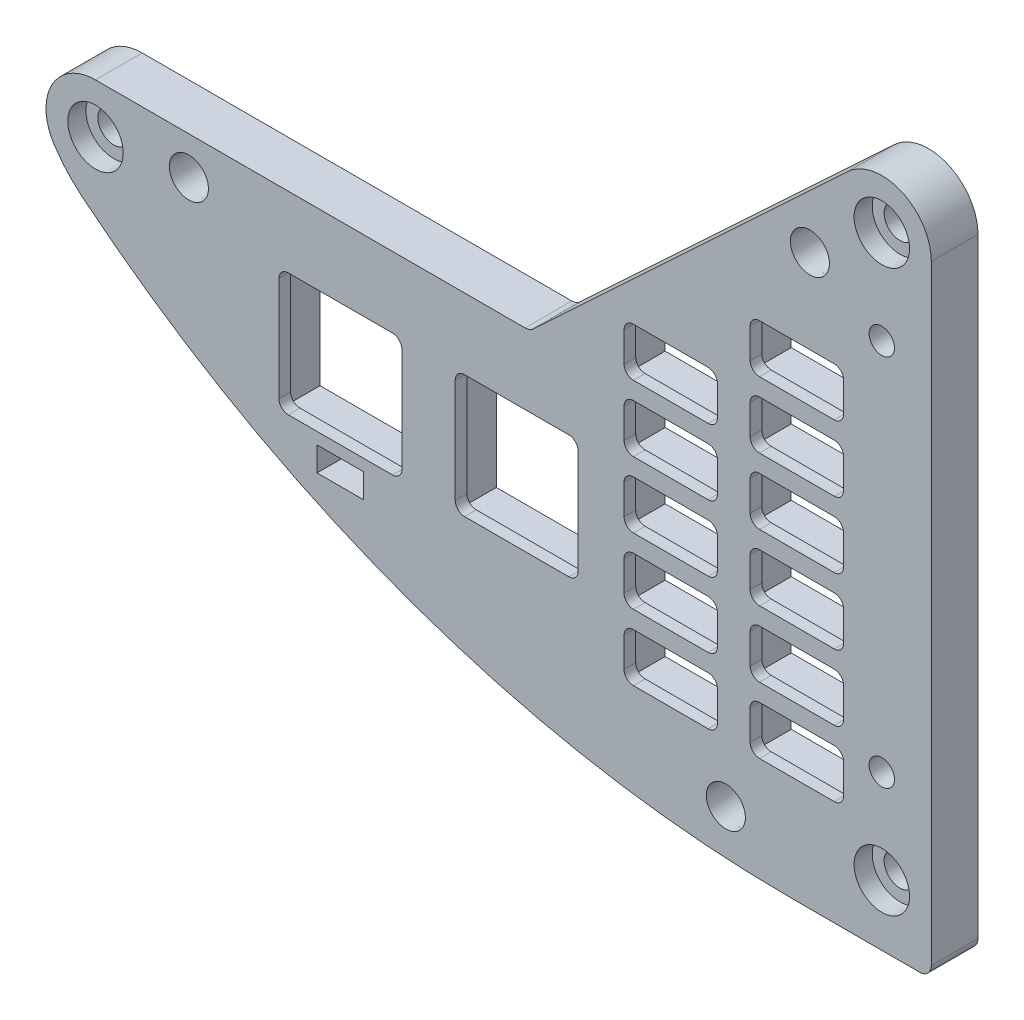
SolidWorks part; units mm, degrees
ref_plane "Front Plane" through (0, 0, 0) normal (0, 0, 1) x (1, 0, 0)
ref_plane "Top Plane" through (0, 0, 0) normal (0, 1, 0) x (1, 0, 0)
ref_plane "Right Plane" through (0, 0, 0) normal (1, 0, 0) x (0, 0, -1)
sketch "Sketch2" plane through (0, 0, -77.851) normal (0, 0, 1) x (1, 0, 0)
  line L0 (-595.8647, 521.6144) -> (-595.8647, 503.8344) construction
  line L1 (-595.8647, 503.8344) -> (-578.0847, 503.8344) construction
  line L2 (-578.0847, 503.8344) -> (-578.0847, 521.6144) construction
  line L3 (-578.0847, 521.6144) -> (-595.8647, 521.6144) construction
  line L4 (-530.5867, 481.6475) -> (-530.5867, 566.1727)
  line L5 (-541.9099, 571.0939) -> (-585.1967, 530.7013)
  line L6 (-585.1967, 530.7013) -> (-644.2517, 530.7013)
  line L7 (-549.6367, 481.6475) -> (-530.5867, 481.6475)
  line L8 (-530.5867, 481.6475) -> (-530.5867, 566.1727)
  line L9 (-541.9099, 571.0939) -> (-585.1967, 530.7013)
  line L10 (-585.1967, 530.7013) -> (-644.2517, 530.7013)
  line L11 (-549.6367, 481.6475) -> (-530.5867, 481.6475)
  line L12 (-572.3697, 495.935) -> (-559.6697, 495.935) construction
  line L13 (-559.6697, 495.935) -> (-559.6697, 502.539) construction
  line L14 (-559.6697, 502.539) -> (-572.3697, 502.539) construction
  line L15 (-572.3697, 502.539) -> (-572.3697, 495.935) construction
  line L16 (-572.3697, 504.9266) -> (-559.6697, 504.9266) construction
  line L17 (-559.6697, 504.9266) -> (-559.6697, 511.5306) construction
  line L18 (-559.6697, 511.5306) -> (-572.3697, 511.5306) construction
  line L19 (-572.3697, 511.5306) -> (-572.3697, 504.9266) construction
  line L20 (-555.2247, 502.539) -> (-555.2247, 495.935) construction
  line L21 (-555.2247, 495.935) -> (-542.5247, 495.935) construction
  line L22 (-542.5247, 495.935) -> (-542.5247, 502.539) construction
  line L23 (-542.5247, 502.539) -> (-555.2247, 502.539) construction
  line L24 (-555.2247, 504.9266) -> (-542.5247, 504.9266) construction
  line L25 (-542.5247, 504.9266) -> (-542.5247, 511.5306) construction
  line L26 (-542.5247, 511.5306) -> (-555.2247, 511.5306) construction
  line L27 (-555.2247, 511.5306) -> (-555.2247, 504.9266) construction
  line L28 (-555.2247, 513.9182) -> (-542.5247, 513.9182) construction
  line L29 (-542.5247, 513.9182) -> (-542.5247, 520.5222) construction
  line L30 (-542.5247, 520.5222) -> (-555.2247, 520.5222) construction
  line L31 (-555.2247, 520.5222) -> (-555.2247, 513.9182) construction
  line L32 (-572.3697, 513.9182) -> (-559.6697, 513.9182) construction
  line L33 (-559.6697, 513.9182) -> (-559.6697, 520.5222) construction
  line L34 (-559.6697, 520.5222) -> (-572.3697, 520.5222) construction
  line L35 (-572.3697, 520.5222) -> (-572.3697, 513.9182) construction
  line L36 (-572.3697, 522.9098) -> (-559.6697, 522.9098) construction
  line L37 (-559.6697, 522.9098) -> (-559.6697, 529.5138) construction
  line L38 (-559.6697, 529.5138) -> (-572.3697, 529.5138) construction
  line L39 (-572.3697, 529.5138) -> (-572.3697, 522.9098) construction
  line L40 (-555.2247, 522.9098) -> (-542.5247, 522.9098) construction
  line L41 (-542.5247, 522.9098) -> (-542.5247, 529.5138) construction
  line L42 (-542.5247, 529.5138) -> (-555.2247, 529.5138) construction
  line L43 (-555.2247, 529.5138) -> (-555.2247, 522.9098) construction
  line L44 (-555.2247, 531.9014) -> (-542.5247, 531.9014) construction
  line L45 (-542.5247, 531.9014) -> (-542.5247, 538.5054) construction
  line L46 (-542.5247, 538.5054) -> (-555.2247, 538.5054) construction
  line L47 (-555.2247, 538.5054) -> (-555.2247, 531.9014) construction
  line L48 (-572.3697, 531.9014) -> (-559.6697, 531.9014) construction
  line L49 (-559.6697, 531.9014) -> (-559.6697, 538.5054) construction
  line L50 (-559.6697, 538.5054) -> (-572.3697, 538.5054) construction
  line L51 (-572.3697, 538.5054) -> (-572.3697, 531.9014) construction
  line L52 (-555.2247, 540.893) -> (-542.5247, 540.893) construction
  line L53 (-542.5247, 540.893) -> (-542.5247, 547.497) construction
  line L54 (-542.5247, 547.497) -> (-555.2247, 547.497) construction
  line L55 (-555.2247, 547.497) -> (-555.2247, 540.893) construction
  line L56 (-555.2247, 513.9182) -> (-542.5247, 513.9182) construction
  line L57 (-595.8647, 521.6144) -> (-595.8647, 503.8344) construction
  line L58 (-595.8647, 503.8344) -> (-578.0847, 503.8344) construction
  line L59 (-578.0847, 503.8344) -> (-578.0847, 521.6144) construction
  line L60 (-578.0847, 521.6144) -> (-595.8647, 521.6144) construction
  line L61 (-572.3697, 495.935) -> (-559.6697, 495.935)
  line L62 (-559.6697, 495.935) -> (-559.6697, 502.539)
  line L63 (-559.6697, 502.539) -> (-572.3697, 502.539)
  line L64 (-572.3697, 502.539) -> (-572.3697, 495.935)
  line L65 (-572.3697, 504.9266) -> (-559.6697, 504.9266)
  line L66 (-559.6697, 504.9266) -> (-559.6697, 511.5306)
  line L67 (-559.6697, 511.5306) -> (-572.3697, 511.5306)
  line L68 (-572.3697, 511.5306) -> (-572.3697, 504.9266)
  line L69 (-555.2247, 502.539) -> (-555.2247, 495.935)
  line L70 (-555.2247, 495.935) -> (-542.5247, 495.935)
  line L71 (-542.5247, 495.935) -> (-542.5247, 502.539)
  line L72 (-542.5247, 502.539) -> (-555.2247, 502.539)
  line L73 (-555.2247, 504.9266) -> (-542.5247, 504.9266)
  line L74 (-542.5247, 504.9266) -> (-542.5247, 511.5306)
  line L75 (-542.5247, 511.5306) -> (-555.2247, 511.5306)
  line L76 (-555.2247, 511.5306) -> (-555.2247, 504.9266)
  line L77 (-555.2247, 513.9182) -> (-542.5247, 513.9182)
  line L78 (-542.5247, 513.9182) -> (-542.5247, 520.5222)
  line L79 (-542.5247, 520.5222) -> (-555.2247, 520.5222)
  line L80 (-555.2247, 520.5222) -> (-555.2247, 513.9182)
  line L81 (-572.3697, 513.9182) -> (-559.6697, 513.9182)
  line L82 (-559.6697, 513.9182) -> (-559.6697, 520.5222)
  line L83 (-559.6697, 520.5222) -> (-572.3697, 520.5222)
  line L84 (-572.3697, 520.5222) -> (-572.3697, 513.9182)
  line L85 (-572.3697, 522.9098) -> (-559.6697, 522.9098)
  line L86 (-559.6697, 522.9098) -> (-559.6697, 529.5138)
  line L87 (-559.6697, 529.5138) -> (-572.3697, 529.5138)
  line L88 (-572.3697, 529.5138) -> (-572.3697, 522.9098)
  line L89 (-555.2247, 522.9098) -> (-542.5247, 522.9098)
  line L90 (-542.5247, 522.9098) -> (-542.5247, 529.5138)
  line L91 (-542.5247, 529.5138) -> (-555.2247, 529.5138)
  line L92 (-555.2247, 529.5138) -> (-555.2247, 522.9098)
  line L93 (-555.2247, 531.9014) -> (-542.5247, 531.9014)
  line L94 (-542.5247, 531.9014) -> (-542.5247, 538.5054)
  line L95 (-542.5247, 538.5054) -> (-555.2247, 538.5054)
  line L96 (-555.2247, 538.5054) -> (-555.2247, 531.9014)
  line L97 (-572.3697, 531.9014) -> (-559.6697, 531.9014)
  line L98 (-559.6697, 531.9014) -> (-559.6697, 538.5054)
  line L99 (-559.6697, 538.5054) -> (-572.3697, 538.5054)
  line L100 (-572.3697, 538.5054) -> (-572.3697, 531.9014)
  line L101 (-555.2247, 540.893) -> (-542.5247, 540.893)
  line L102 (-542.5247, 540.893) -> (-542.5247, 547.497)
  line L103 (-542.5247, 547.497) -> (-555.2247, 547.497)
  line L104 (-555.2247, 547.497) -> (-555.2247, 540.893)
  line L105 (-555.2247, 513.9182) -> (-542.5247, 513.9182)
  line L106 (-578.0847, 503.8344) -> (-595.8647, 521.6144) construction
  line L108 (-578.6181, 521.081) -> (-595.3313, 521.081)
  line L109 (-578.6181, 521.081) -> (-578.6181, 504.3678)
  line L110 (-578.6181, 504.3678) -> (-595.3313, 504.3678)
  line L111 (-595.3313, 521.081) -> (-595.3313, 504.3678)
  line L112 (-578.6181, 521.081) -> (-595.3313, 504.3678) construction
  line L113 (-578.6181, 504.3678) -> (-595.3313, 521.081) construction
  arc A4 (-530.5867, 566.1727) -> (-541.9099, 571.0939) centre (-537.3177, 566.1727) ccw
  arc A5 (-644.2517, 530.7013) -> (-649.8762, 520.2727) centre (-644.2517, 523.9703) ccw
  arc A6 (-649.8762, 520.2727) -> (-646.0191, 515.9958) centre (-634.0129, 530.7013) ccw
  arc A7 (-646.0191, 515.9958) -> (-549.6367, 481.6475) centre (-549.6367, 634.0475) ccw
  arc A8 (-530.5867, 566.1727) -> (-541.9099, 571.0939) centre (-537.3177, 566.1727) ccw
  arc A9 (-644.2517, 530.7013) -> (-649.8762, 520.2727) centre (-644.2517, 523.9703) ccw
  arc A10 (-649.8762, 520.2727) -> (-646.0191, 515.9958) centre (-634.0129, 530.7013) ccw
  arc A11 (-646.0191, 515.9958) -> (-549.6367, 481.6475) centre (-549.6367, 634.0475) ccw
  point P58 (-586.9747, 512.7244)
  dimension "D2" = 16.7132
  dimension "D1" = 0
extrude "Boss-Extrude1" add sketch "Sketch2" against normal blind 6.35 contours A10 A11 L11 L8 A8 L9 L10 A9 L60 L59 L58 L57 L64 L63 L62 L61 L68 L67 L66 L65 L72 L71 L70 L69 L76 L75 L74 L73 L80 L79 L78 L77 L84 L83 L82 L81 L88 L87 L86 L85 L92 L91 region at (-576.7506, 517.828, -77.851)
hole_wizard "CBORE for #6 Pan Head Machine Screw1" positions "Sketch4" profile "Sketch3" counterbore size "#6" standard "ANSI Inch" end condition through all
sketch "Sketch4" plane through (0, 0, -77.851) normal (0, 0, 1) x (1, 0, 0)
  point P0 (-537.3177, 489.9025)
  point P3 (-537.3177, 566.1727)
  point P6 (-644.2517, 523.9703)
sketch "Sketch3" plane through (-537.3177, 489.9025, -77.851) normal (1, 0, 0) x (0, -1, 0)
  line L0 (0, 0) -> (0, 6.35)
  line L1 (0, 6.35) -> (2.1526, 6.35)
  line L3 (2.1526, 6.35) -> (2.1526, 2.4638)
  line L4 (2.1526, 2.4638) -> (3.7706, 2.4638)
  line L5 (3.7706, 2.4638) -> (3.7706, 0)
  line L7 (3.7706, 0) -> (0, 0)
  line L11 (0, -6.35) -> (0, 107.95) construction
  dimension "Thru Hole Dia." = 4.3053
  dimension "Thru Hole Depth" = 6.35
  dimension "C'Bore Dia." = 7.5413
  dimension "C'Bore Depth" = 2.4638
hole_wizard "#6 Threaded Insert Tapered Hole" positions "Sketch6" profile "Sketch5" legacy
sketch "Sketch6" plane through (0, 0, -77.851) normal (0, 0, 1) x (1, 0, 0)
  point P0 (-558.5267, 487.9975)
  point P3 (-547.0967, 558.9583)
  point P6 (-631.5517, 525.5578)
sketch "Sketch5" plane through (-558.5267, 487.9975, -77.851) normal (1, 0, 0) x (0, -1, 0)
  line L0 (0, 0) -> (0, 3.81)
  line L1 (0, 3.81) -> (2.5273, 3.81)
  line L2 (2.5273, 3.81) -> (2.6543, 0)
  line L3 (2.6543, 0) -> (0, 0)
  line L4 (0, 110) -> (0, -10) construction
  dimension "Minor Diameter" = 5.0546
  dimension "Depth" = 3.81
  dimension "Major Diameter" = 5.3086
sketch "Sketch7" plane through (0, 0, -77.851) normal (0, 0, 1) x (1, 0, 0)
  line L0 (-610.9485, 512.7244) -> (-610.9485, 521.081) construction
  line L2 (-610.9485, 512.7244) -> (-595.3313, 512.7244) construction
  line L3 (-602.5919, 504.3678) -> (-619.3051, 504.3678)
  line L4 (-602.5919, 504.3678) -> (-602.5919, 521.081)
  line L5 (-602.5919, 521.081) -> (-619.3051, 521.081)
  line L6 (-619.3051, 504.3678) -> (-619.3051, 521.081)
  line L7 (-602.5919, 504.3678) -> (-619.3051, 521.081) construction
  line L8 (-602.5919, 521.081) -> (-619.3051, 504.3678) construction
  line L9 (-595.3313, 521.081) -> (-595.3313, 504.3678) construction
  point P5 (-610.9485, 512.7244)
  dimension "D1" = 16.7132
  dimension "D2" = 16.7132
  dimension "D3" = 15.6171
extrude "Cut-Extrude1" cut sketch "Sketch7" against normal through all
sketch "Sketch8" plane through (0, 0, -84.201) normal (0, 0, -1) x (-1, 0, 0)
  line L0 (555.9867, 540.131) -> (555.9867, 548.259)
  line L1 (555.9867, 548.259) -> (541.7627, 548.259)
  line L2 (541.7627, 548.259) -> (541.7627, 540.131)
  line L3 (541.7627, 540.131) -> (555.9867, 540.131)
  line L4 (555.2247, 540.893) -> (555.2247, 547.497)
  line L5 (542.5247, 540.893) -> (555.2247, 540.893)
  line L6 (542.5247, 547.497) -> (542.5247, 540.893)
  line L7 (555.2247, 547.497) -> (542.5247, 547.497)
  line L8 (555.2247, 540.893) -> (555.2247, 547.497) construction
  line L9 (542.5247, 540.893) -> (555.2247, 540.893) construction
  line L10 (542.5247, 547.497) -> (542.5247, 540.893) construction
  line L11 (555.2247, 547.497) -> (542.5247, 547.497) construction
  line L12 (555.2247, 531.9014) -> (555.2247, 538.5054)
  line L13 (542.5247, 531.9014) -> (555.2247, 531.9014)
  line L14 (542.5247, 538.5054) -> (542.5247, 531.9014)
  line L15 (555.2247, 538.5054) -> (542.5247, 538.5054)
  line L16 (555.2247, 531.9014) -> (555.2247, 538.5054) construction
  line L17 (542.5247, 531.9014) -> (555.2247, 531.9014) construction
  line L18 (542.5247, 538.5054) -> (542.5247, 531.9014) construction
  line L19 (555.2247, 538.5054) -> (542.5247, 538.5054) construction
  line L20 (555.2247, 522.9098) -> (555.2247, 529.5138)
  line L21 (542.5247, 522.9098) -> (555.2247, 522.9098)
  line L22 (542.5247, 529.5138) -> (542.5247, 522.9098)
  line L23 (555.2247, 529.5138) -> (542.5247, 529.5138)
  line L24 (555.2247, 522.9098) -> (555.2247, 529.5138) construction
  line L25 (542.5247, 522.9098) -> (555.2247, 522.9098) construction
  line L26 (542.5247, 529.5138) -> (542.5247, 522.9098) construction
  line L27 (555.2247, 529.5138) -> (542.5247, 529.5138) construction
  line L28 (555.2247, 513.9182) -> (555.2247, 520.5222)
  line L29 (542.5247, 513.9182) -> (555.2247, 513.9182)
  line L30 (542.5247, 520.5222) -> (542.5247, 513.9182)
  line L31 (555.2247, 520.5222) -> (542.5247, 520.5222)
  line L32 (555.2247, 513.9182) -> (555.2247, 520.5222) construction
  line L33 (542.5247, 513.9182) -> (555.2247, 513.9182) construction
  line L34 (542.5247, 520.5222) -> (542.5247, 513.9182) construction
  line L35 (555.2247, 520.5222) -> (542.5247, 520.5222) construction
  line L36 (555.2247, 504.9266) -> (555.2247, 511.5306)
  line L37 (542.5247, 504.9266) -> (555.2247, 504.9266)
  line L38 (542.5247, 511.5306) -> (542.5247, 504.9266)
  line L39 (555.2247, 511.5306) -> (542.5247, 511.5306)
  line L40 (555.2247, 504.9266) -> (555.2247, 511.5306) construction
  line L41 (542.5247, 504.9266) -> (555.2247, 504.9266) construction
  line L42 (542.5247, 511.5306) -> (542.5247, 504.9266) construction
  line L43 (555.2247, 511.5306) -> (542.5247, 511.5306) construction
  line L44 (555.2247, 502.539) -> (542.5247, 502.539)
  line L45 (555.2247, 495.935) -> (555.2247, 502.539)
  line L46 (542.5247, 495.935) -> (555.2247, 495.935)
  line L47 (542.5247, 502.539) -> (542.5247, 495.935)
  line L48 (555.2247, 502.539) -> (542.5247, 502.539) construction
  line L49 (555.2247, 495.935) -> (555.2247, 502.539) construction
  line L50 (542.5247, 495.935) -> (555.2247, 495.935) construction
  line L51 (542.5247, 502.539) -> (542.5247, 495.935) construction
  line L52 (572.3697, 531.9014) -> (572.3697, 538.5054)
  line L53 (559.6697, 531.9014) -> (572.3697, 531.9014)
  line L54 (559.6697, 538.5054) -> (559.6697, 531.9014)
  line L55 (572.3697, 538.5054) -> (559.6697, 538.5054)
  line L56 (572.3697, 531.9014) -> (572.3697, 538.5054) construction
  line L57 (559.6697, 531.9014) -> (572.3697, 531.9014) construction
  line L58 (559.6697, 538.5054) -> (559.6697, 531.9014) construction
  line L59 (572.3697, 538.5054) -> (559.6697, 538.5054) construction
  line L60 (572.3697, 522.9098) -> (572.3697, 529.5138)
  line L61 (559.6697, 522.9098) -> (572.3697, 522.9098)
  line L62 (559.6697, 529.5138) -> (559.6697, 522.9098)
  line L63 (572.3697, 529.5138) -> (559.6697, 529.5138)
  line L64 (572.3697, 522.9098) -> (572.3697, 529.5138) construction
  line L65 (559.6697, 522.9098) -> (572.3697, 522.9098) construction
  line L66 (559.6697, 529.5138) -> (559.6697, 522.9098) construction
  line L67 (572.3697, 529.5138) -> (559.6697, 529.5138) construction
  line L68 (572.3697, 513.9182) -> (572.3697, 520.5222)
  line L69 (559.6697, 513.9182) -> (572.3697, 513.9182)
  line L70 (559.6697, 520.5222) -> (559.6697, 513.9182)
  line L71 (572.3697, 520.5222) -> (559.6697, 520.5222)
  line L72 (572.3697, 513.9182) -> (572.3697, 520.5222) construction
  line L73 (559.6697, 513.9182) -> (572.3697, 513.9182) construction
  line L74 (559.6697, 520.5222) -> (559.6697, 513.9182) construction
  line L75 (572.3697, 520.5222) -> (559.6697, 520.5222) construction
  line L76 (572.3697, 504.9266) -> (572.3697, 511.5306)
  line L77 (559.6697, 504.9266) -> (572.3697, 504.9266)
  line L78 (559.6697, 511.5306) -> (559.6697, 504.9266)
  line L79 (572.3697, 511.5306) -> (559.6697, 511.5306)
  line L80 (572.3697, 504.9266) -> (572.3697, 511.5306) construction
  line L81 (559.6697, 504.9266) -> (572.3697, 504.9266) construction
  line L82 (559.6697, 511.5306) -> (559.6697, 504.9266) construction
  line L83 (572.3697, 511.5306) -> (559.6697, 511.5306) construction
  line L84 (572.3697, 495.935) -> (572.3697, 502.539)
  line L85 (559.6697, 495.935) -> (572.3697, 495.935)
  line L86 (559.6697, 502.539) -> (559.6697, 495.935)
  line L87 (572.3697, 502.539) -> (559.6697, 502.539)
  line L88 (572.3697, 495.935) -> (572.3697, 502.539) construction
  line L89 (559.6697, 495.935) -> (572.3697, 495.935) construction
  line L90 (559.6697, 502.539) -> (559.6697, 495.935) construction
  line L91 (572.3697, 502.539) -> (559.6697, 502.539) construction
  line L92 (595.3313, 504.3678) -> (595.3313, 521.081)
  line L93 (578.6181, 504.3678) -> (595.3313, 504.3678)
  line L94 (578.6181, 521.081) -> (578.6181, 504.3678)
  line L95 (595.3313, 521.081) -> (578.6181, 521.081)
  line L96 (595.3313, 504.3678) -> (595.3313, 521.081) construction
  line L97 (578.6181, 504.3678) -> (595.3313, 504.3678) construction
  line L98 (578.6181, 521.081) -> (578.6181, 504.3678) construction
  line L99 (595.3313, 521.081) -> (578.6181, 521.081) construction
  line L100 (555.9867, 531.1394) -> (555.9867, 539.2674)
  line L101 (555.9867, 539.2674) -> (541.7627, 539.2674)
  line L102 (541.7627, 539.2674) -> (541.7627, 531.1394)
  line L103 (541.7627, 531.1394) -> (555.9867, 531.1394)
  line L104 (555.9867, 522.1478) -> (555.9867, 530.2758)
  line L105 (555.9867, 530.2758) -> (541.7627, 530.2758)
  line L106 (541.7627, 530.2758) -> (541.7627, 522.1478)
  line L107 (541.7627, 522.1478) -> (555.9867, 522.1478)
  line L108 (555.9867, 513.1562) -> (555.9867, 521.2842)
  line L109 (555.9867, 521.2842) -> (541.7627, 521.2842)
  line L110 (541.7627, 521.2842) -> (541.7627, 513.1562)
  line L111 (541.7627, 513.1562) -> (555.9867, 513.1562)
  line L112 (555.9867, 504.1646) -> (555.9867, 512.2926)
  line L113 (555.9867, 512.2926) -> (541.7627, 512.2926)
  line L114 (541.7627, 512.2926) -> (541.7627, 504.1646)
  line L115 (541.7627, 504.1646) -> (555.9867, 504.1646)
  line L116 (555.9867, 503.301) -> (541.7627, 503.301)
  line L117 (541.7627, 503.301) -> (541.7627, 495.173)
  line L118 (541.7627, 495.173) -> (555.9867, 495.173)
  line L119 (555.9867, 495.173) -> (555.9867, 503.301)
  line L120 (573.1317, 531.1394) -> (573.1317, 539.2674)
  line L121 (573.1317, 539.2674) -> (558.9077, 539.2674)
  line L122 (558.9077, 539.2674) -> (558.9077, 531.1394)
  line L123 (558.9077, 531.1394) -> (573.1317, 531.1394)
  line L124 (573.1317, 522.1478) -> (573.1317, 530.2758)
  line L125 (573.1317, 530.2758) -> (558.9077, 530.2758)
  line L126 (558.9077, 530.2758) -> (558.9077, 522.1478)
  line L127 (558.9077, 522.1478) -> (573.1317, 522.1478)
  line L128 (573.1317, 513.1562) -> (573.1317, 521.2842)
  line L129 (573.1317, 521.2842) -> (558.9077, 521.2842)
  line L130 (558.9077, 521.2842) -> (558.9077, 513.1562)
  line L131 (558.9077, 513.1562) -> (573.1317, 513.1562)
  line L132 (573.1317, 504.1646) -> (573.1317, 512.2926)
  line L133 (573.1317, 512.2926) -> (558.9077, 512.2926)
  line L134 (558.9077, 512.2926) -> (558.9077, 504.1646)
  line L135 (558.9077, 504.1646) -> (573.1317, 504.1646)
  line L136 (573.1317, 495.173) -> (573.1317, 503.301)
  line L137 (573.1317, 503.301) -> (558.9077, 503.301)
  line L138 (558.9077, 503.301) -> (558.9077, 495.173)
  line L139 (558.9077, 495.173) -> (573.1317, 495.173)
  line L140 (596.0933, 503.6058) -> (596.0933, 521.843)
  line L141 (596.0933, 521.843) -> (577.8561, 521.843)
  line L142 (577.8561, 521.843) -> (577.8561, 503.6058)
  line L143 (577.8561, 503.6058) -> (596.0933, 503.6058)
  line L144 (620.0671, 521.843) -> (601.8299, 521.843)
  line L145 (601.8299, 521.843) -> (601.8299, 503.6058)
  line L146 (601.8299, 503.6058) -> (620.0671, 503.6058)
  line L147 (620.0671, 503.6058) -> (620.0671, 521.843)
  line L148 (619.3051, 521.081) -> (602.5919, 521.081)
  line L149 (619.3051, 504.3678) -> (619.3051, 521.081)
  line L150 (602.5919, 504.3678) -> (619.3051, 504.3678)
  line L151 (602.5919, 521.081) -> (602.5919, 504.3678)
  line L152 (619.3051, 521.081) -> (602.5919, 521.081) construction
  line L153 (619.3051, 504.3678) -> (619.3051, 521.081) construction
  line L154 (602.5919, 504.3678) -> (619.3051, 504.3678) construction
  line L155 (602.5919, 521.081) -> (602.5919, 504.3678) construction
  dimension "D1" = 0
  dimension "D2" = 0
  dimension "D3" = 0
  dimension "D4" = 0
  dimension "D5" = 0
  dimension "D6" = 0
  dimension "D7" = 0
  dimension "D8" = 0
  dimension "D9" = 0
  dimension "D10" = 0
  dimension "D11" = 0
  dimension "D12" = 0
  dimension "D13" = 0.762
  dimension "D14" = 0
  dimension "D15" = 0.762
extrude "Cut-Extrude2" cut sketch "Sketch8" against normal offset from surface (4.7625 mm away) 1.5875 up to face at (-610.9485, 512.7244, -77.851)
fillet "Fillet1" radius 1.5875 2 edges at (-585.1967, 530.7013, -81.026) (-530.5867, 481.6475, -81.026)
hole_wizard "#4 Clearance Hole1" positions "Sketch10" profile "Sketch9" hole size "#4" standard "ANSI Inch" end condition through all
sketch "Sketch10" plane through (0, 0, -77.851) normal (0, 0, 1) x (1, 0, 0)
  point P0 (-537.3177, 502.6376)
  point P3 (-537.3177, 553.4376)
sketch "Sketch9" plane through (-537.3177, 502.6376, -77.851) normal (1, 0, 0) x (0, -1, 0)
  line L0 (0, 0) -> (0, 6.35)
  line L1 (0, 6.35) -> (1.7272, 6.35)
  line L2 (1.7272, 6.35) -> (1.7272, 0)
  line L5 (1.7272, 0) -> (0, 0)
  line L11 (0, -6.35) -> (0, 107.95) construction
  dimension "Thru Hole Dia." = 3.4544
  dimension "Thru Hole Depth" = 6.35
hole_wizard "Hole2" positions "Sketch12" profile "Sketch11" legacy
sketch "Sketch12" plane through (0, 0, -84.201) normal (0, 0, -1) x (-1, 0, 0)
  point P0 (642.6555, 517.9926)
sketch "Sketch11" plane through (-642.6555, 517.9926, -84.201) normal (1, 0, 0) x (0, 1, 0)
  line L0 (0, 0) -> (0, 3.429)
  line L1 (0, 3.429) -> (1.9431, 3.429)
  line L2 (1.9431, 3.429) -> (2.0701, 0)
  line L3 (2.0701, 0) -> (0, 0)
  line L4 (0, 110) -> (0, -10) construction
  dimension "Minor Diameter" = 3.8862
  dimension "Depth" = 3.429
  dimension "Major Diameter" = 4.1402
hole_wizard "#4 Clearance Hole2" positions "Sketch14" profile "Sketch13" hole size "#4" standard "ANSI Inch"
sketch "Sketch14" plane through (0, 0, -80.772) normal (0, 0, -1) x (-1, 0, 0)
  point P2 (642.6555, 517.9926)
sketch "Sketch13" plane through (-642.6555, 517.9926, -80.772) normal (1, 0, 0) x (0, 1, 0)
  line L0 (0, 0) -> (0, 1.5875)
  line L1 (0, 1.5875) -> (1.7272, 1.5875)
  line L2 (1.7272, 1.5875) -> (1.7272, 0)
  line L5 (1.7272, 0) -> (0, 0)
  line L10 (0, 1.5875) -> (-1.7272, 1.5875) construction
  line L11 (0, -6.35) -> (0, 107.95) construction
  dimension "Hole Dia." = 3.4544
  dimension "Hole Depth" = 1.5875
  dimension "Drill Angle" = 180
hole_wizard "#6 Clearance Hole1" positions "Sketch16" profile "Sketch15" hole size "#6" standard "ANSI Inch" end condition through all
sketch "Sketch16" plane through (0, 0, -81.661) normal (0, 0, 1) x (1, 0, 0)
  point P0 (-558.5267, 487.9975)
  point P3 (-631.5517, 525.5578)
  point P6 (-547.0967, 558.9583)
sketch "Sketch15" plane through (-558.5267, 487.9975, -81.661) normal (1, 0, 0) x (0, -1, 0)
  line L0 (0, 0) -> (0, 2.54)
  line L1 (0, 2.54) -> (2.1526, 2.54)
  line L2 (2.1526, 2.54) -> (2.1526, 0)
  line L5 (2.1526, 0) -> (0, 0)
  line L11 (0, -6.35) -> (0, 107.95) construction
  dimension "Thru Hole Dia." = 4.3053
  dimension "Thru Hole Depth" = 2.54
sketch "Sketch17" plane through (0, 0, -77.851) normal (0, 0, 1) x (1, 0, 0)
  line L0 (-610.9485, 504.3678) -> (-610.9485, 494.5246) construction
  line L1 (-607.7735, 499.4783) -> (-614.1235, 499.4783)
  line L2 (-607.7735, 499.4783) -> (-607.7735, 502.7803)
  line L3 (-607.7735, 502.7803) -> (-614.1235, 502.7803)
  line L4 (-614.1235, 499.4783) -> (-614.1235, 502.7803)
  line L5 (-619.3051, 504.3678) -> (-602.5919, 504.3678) construction
  arc A0 (-646.0191, 515.9958) -> (-549.6367, 481.6475) centre (-549.6367, 634.0475) ccw construction
  point P11 (-610.9485, 499.4783)
  dimension "D1" = 3.302
  dimension "D2" = 6.35
  dimension "D3" = 1.5875
extrude "Cut-Extrude3" cut sketch "Sketch17" against normal through all
fillet "Fillet2" radius 1.27 52 edges at (-595.3313, 504.3678, -78.6448) (-578.6181, 504.3678, -78.6448) (-578.6181, 521.081, -78.6448) (-595.3313, 521.081, -78.6448) (-555.2247, 540.893, -78.6448) (-542.5247, 540.893, -78.6448) (-542.5247, 547.497, -78.6448) (-555.2247, 547.497, -78.6448) (-572.3697, 531.9014, -78.6448) (-559.6697, 531.9014, -78.6448) (-559.6697, 538.5054, -78.6448) (-572.3697, 538.5054, -78.6448) (-555.2247, 531.9014, -78.6448) (-542.5247, 531.9014, -78.6448) (-542.5247, 538.5054, -78.6448) (-555.2247, 538.5054, -78.6448) (-555.2247, 522.9098, -78.6448) (-542.5247, 522.9098, -78.6447) (-542.5247, 529.5138, -78.6448) (-555.2247, 529.5138, -78.6448) (-572.3697, 522.9098, -78.6448) (-559.6697, 522.9098, -78.6448) (-559.6697, 529.5138, -78.6448) (-572.3697, 529.5138, -78.6448) (-572.3697, 513.9182, -78.6448) (-559.6697, 513.9182, -78.6447) (-559.6697, 520.5222, -78.6448) (-572.3697, 520.5222, -78.6448) (-555.2247, 513.9182, -78.6447) (-542.5247, 513.9182, -78.6447) (-542.5247, 520.5222, -78.6447) (-555.2247, 520.5222, -78.6448) (-555.2247, 504.9266, -78.6447) (-542.5247, 504.9266, -78.6448) (-542.5247, 511.5306, -78.6447) (-555.2247, 511.5306, -78.6447) (-555.2247, 502.539, -78.6448) (-555.2247, 495.935, -78.6448) (-572.3697, 504.9266, -78.6448) (-559.6697, 504.9266, -78.6447) (-559.6697, 511.5306, -78.6447) (-572.3697, 511.5306, -78.6448) (-572.3697, 495.935, -78.6448) (-559.6697, 495.935, -78.6448) (-559.6697, 502.539, -78.6447) (-572.3697, 502.539, -78.6448) (-619.3051, 504.3678, -78.6448) (-602.5919, 504.3678, -78.6448) (-602.5919, 521.081, -78.6448) (-619.3051, 521.081, -78.6448) (-542.5247, 495.935, -78.6448) (-542.5247, 502.539, -78.6448)
equation "\"D2@Sketch7\"=\"D1@Sketch7\""
